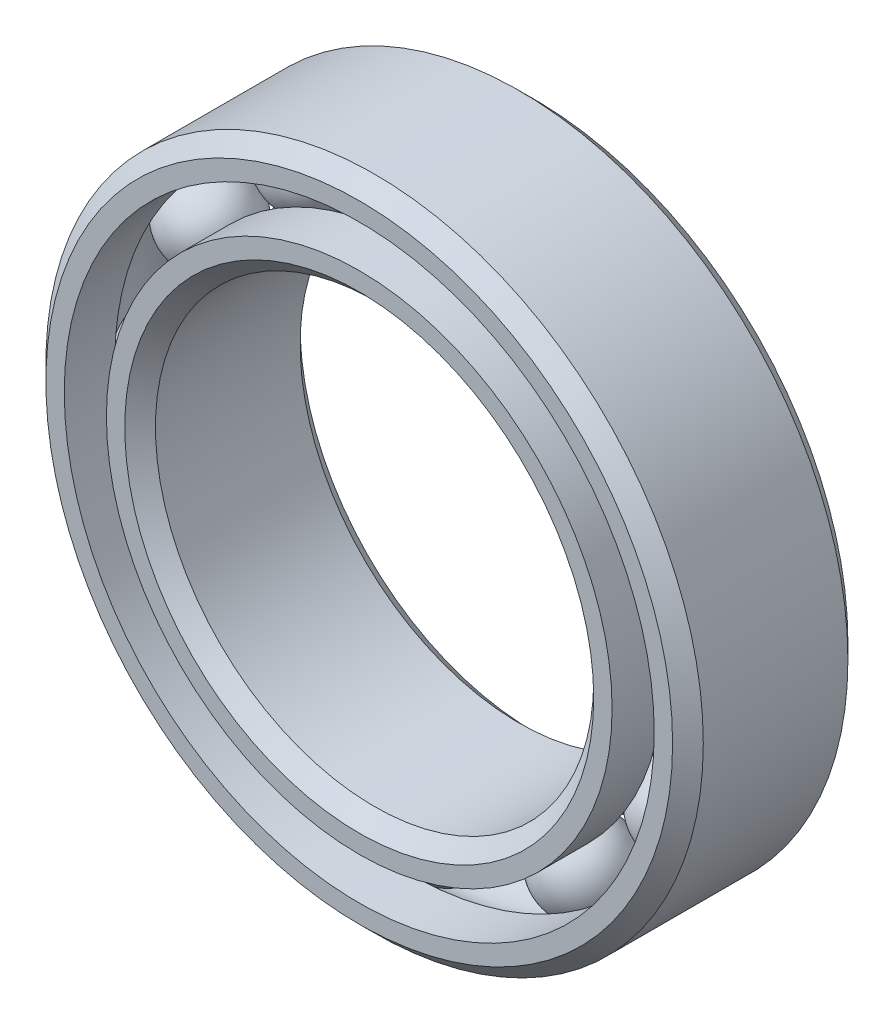
SolidWorks part; units mm, degrees
ref_plane "Front Plane" through (0, 0, 0) normal (0, 0, 1) x (1, 0, 0)
ref_plane "Top Plane" through (0, 0, 0) normal (0, 1, 0) x (1, 0, 0)
ref_plane "Right Plane" through (0, 0, 0) normal (1, 0, 0) x (0, 0, -1)
sketch "Sketch1" plane through (0, 0, 0) normal (1, 0, 0) x (0, 0, -1)
  line L0 (-2, 0) -> (2, 0) construction
  line L1 (0, 7.5) -> (0, -7.5) construction
  line L2 (1.65, 7.5) -> (-1.65, 7.5)
  line L3 (-1.65, 7.5) -> (-2, 7.15)
  line L4 (-2, 7.15) -> (-2, 6.7308)
  line L5 (-2, 6.7308) -> (-0.8493, 6.7308)
  line L6 (2, 6.7308) -> (0.8493, 6.7308)
  line L7 (2, 7.15) -> (2, 6.7308)
  line L8 (1.65, 7.5) -> (2, 7.15)
  line L9 (0, 7.5) -> (0, 6.25) construction
  line L10 (0, 6.25) -> (0, 5) construction
  arc A0 (-0.8493, 6.7308) -> (0.8493, 6.7308) centre (0, 6.25) cw
  point P14 (0, 5)
  point P15 (0.8493, 6.7308)
  dimension "Width" = 4
  dimension "OD" = 15
  dimension "D1" = 45
  dimension "D2" = 0.35
  dimension "Shaft Dia" = 10
revolve "Revolve1" add sketch "Sketch1" angle 360 about L0
sketch "Sketch3" plane through (0, 0, 0) normal (1, 0, 0) x (0, 0, -1)
  line L0 (-2, 5.7692) -> (-0.8493, 5.7692)
  line L1 (0, 7.5) -> (0, -7.5) construction
  line L2 (-2, 7.15) -> (-2, 6.7308) construction
  line L3 (-2, 5.7692) -> (-2, 5.35)
  line L4 (-1.65, 7.5) -> (-2, 7.15) construction
  line L5 (-2, 5.35) -> (-1.65, 5)
  line L6 (-1.65, 5) -> (1.65, 5)
  line L7 (1.65, 7.5) -> (1.65, -7.5) construction
  line L8 (1.65, 5) -> (2, 5.35)
  line L9 (2, -7.15) -> (2, 7.15) construction
  line L10 (2, 5.35) -> (2, 5.7692)
  line L11 (2, 5.7692) -> (0.8493, 5.7692)
  line L13 (1.65, 7.5) -> (2, 7.15) construction
  arc A0 (0.8493, 6.7308) -> (-0.8493, 6.7308) centre (0, 6.25) ccw construction
  arc A1 (0.8493, 5.7692) -> (-0.8493, 5.7692) centre (0, 6.25) cw
revolve "Revolve3" add sketch "Sketch3" angle 360 about L0
sketch "Sketch4" plane through (0, 0, 0) normal (1, 0, 0) x (0, 0, -1)
  line L0 (-0.976, 6.25) -> (0.976, 6.25)
  arc A2 (-0.976, 6.25) -> (0.976, 6.25) centre (0, 6.25) cw
  arc A3 (0.8493, 6.7308) -> (-0.8493, 6.7308) centre (0, 6.25) ccw construction
revolve "Revolve4" add sketch "Sketch4" angle 360 about L0
ref_axis "Axis1" through (0, 0, -2) along (0, 0, 1)
pattern_circular "CirPattern1" count 12 over 360 about axis through (0, 0, -2) along (0, 0, 1) of bodies 104
sketch "Sketch5" plane through (0, 0, 0) normal (1, 0, 0) x (0, 0, -1)
  line L0 (-2, 6.7308) -> (-0.8493, 6.7308) construction
  line L1 (-1.825, 6.7308) -> (-0.976, 6.7308)
  line L2 (-1.825, 6.7308) -> (-1.825, 5.7692)
  line L3 (-1.825, 5.7692) -> (-0.976, 5.7692)
  line L4 (-0.976, 6.7308) -> (-0.976, 5.7692)
  line L5 (-2, 5.7692) -> (-0.8493, 5.7692) construction
  line L6 (2, 6.7308) -> (0.8493, 6.7308) construction
  line L7 (1.825, 6.7308) -> (0.976, 6.7308)
  line L8 (1.825, 6.7308) -> (1.825, 5.7692)
  line L9 (1.825, 5.7692) -> (0.976, 5.7692)
  line L10 (0.976, 6.7308) -> (0.976, 5.7692)
  line L11 (2, 5.7692) -> (0.8493, 5.7692) construction
  line L12 (-1.65, 7.5) -> (-2, 7.15) construction
  point P18 (-1.825, 7.325)
equation "\"D2@Sketch1\" = \"Width@Sketch1\"*.05"
equation "\"D2@CirPattern1\" = 360/\"Balls@CirPattern1\""
